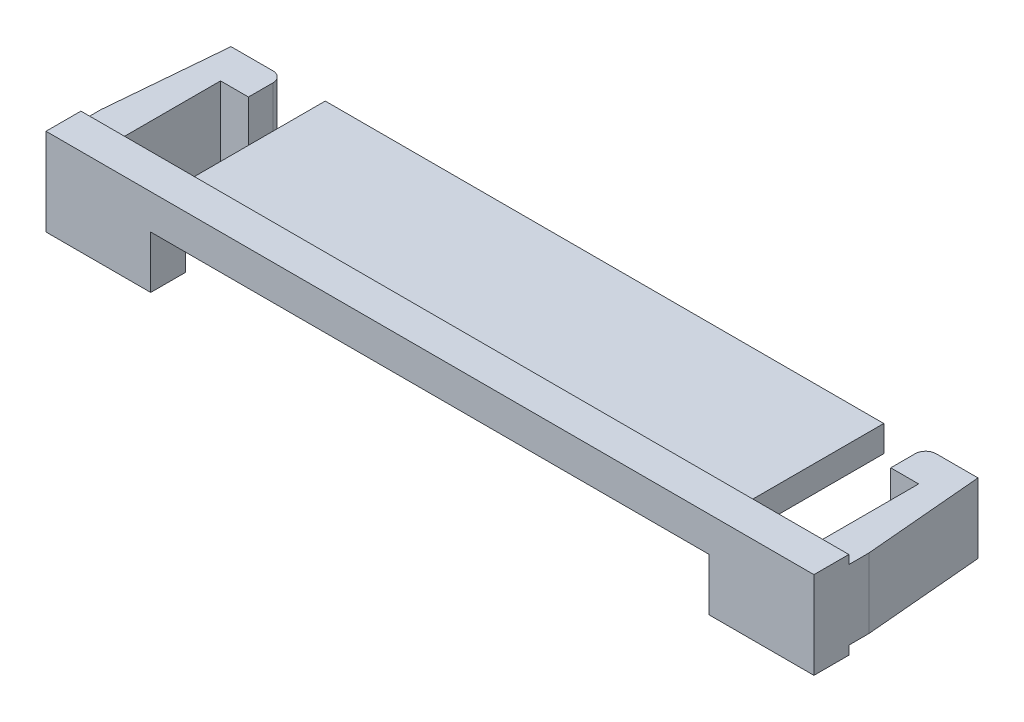
SolidWorks part; units mm, degrees
ref_plane "Front Plane" through (0, 0, 0) normal (0, 0, 1) x (1, 0, 0)
ref_plane "Top Plane" through (0, 0, 0) normal (0, 1, 0) x (1, 0, 0)
ref_plane "Right Plane" through (0, 0, 0) normal (1, 0, 0) x (0, 0, -1)
sketch "Sketch1" plane through (0, 0, 0) normal (0, 0, 1) x (1, 0, 0)
  line L1 (-11, 1.25) -> (11, 1.25)
  line L2 (-11, 1.25) -> (-11, -1.25)
  line L3 (-11, -1.25) -> (11, -1.25)
  line L4 (11, 1.25) -> (11, -1.25)
  line L5 (-11, 1.25) -> (11, -1.25) construction
  line L6 (-11, -1.25) -> (11, 1.25) construction
  point P0 (0, 0)
  dimension "D1" = 22
  dimension "D2" = 2.5
extrude "Boss-Extrude1" add sketch "Sketch1" along normal blind 5
sketch "Sketch2" plane through (0, 0, 0) normal (0, 0, -1) x (-1, 0, 0)
  line L0 (11, 1.25) -> (11, -1.25) construction
  line L1 (-11, 1.25) -> (11, 1.25)
  line L2 (-11, 1.25) -> (-11, 1)
  line L3 (-11, 1) -> (11, 1)
  line L4 (11, 1.25) -> (11, 1)
  line L5 (-11, -1.25) -> (-11, 1.25) construction
  line L6 (11, -1.25) -> (-11, -1.25)
  line L7 (11, -1.25) -> (11, -1)
  line L8 (11, -1) -> (-11, -1)
  line L9 (-11, -1.25) -> (-11, -1)
  dimension "D1" = 0.25
  dimension "D2" = 0.25
extrude "Cut-Extrude1" cut sketch "Sketch2" against normal blind 4
sketch "Sketch3" plane through (0, 0, 0) normal (0, 0, -1) x (-1, 0, 0)
  line L0 (-11, 1) -> (11, 1) construction
  line L1 (-10, 1) -> (-8, 1)
  line L2 (-10, 1) -> (-10, -1)
  line L3 (-10, -1) -> (-8, -1)
  line L4 (-8, 1) -> (-8, -1)
  line L5 (11, -1) -> (-11, -1) construction
  line L6 (-11, -1) -> (-11, 1) construction
  line L7 (10, 1) -> (8, 1)
  line L8 (10, 1) -> (10, -1)
  line L9 (10, -1) -> (8, -1)
  line L10 (8, 1) -> (8, -1)
  line L11 (11, 1) -> (11, -1) construction
  dimension "D1" = 1
  dimension "D2" = 1
  dimension "D3" = 2
  dimension "D4" = 2
extrude "Cut-Extrude2" cut sketch "Sketch3" against normal blind 4
sketch "Sketch5" plane through (0, 0, 0) normal (0, 0, -1) x (-1, 0, 0)
  line L0 (-8, -1) -> (-8, 1) construction
  line L1 (-8, 0.25) -> (8, 0.25)
  line L2 (-8, 0.25) -> (-8, -1.25)
  line L3 (-8, -1.25) -> (8, -1.25)
  line L4 (8, 0.25) -> (8, -1.25)
  line L5 (-11, -1.25) -> (11, -1.25) construction
  line L6 (8, 1) -> (8, -1) construction
  line L7 (11, 1.25) -> (-11, 1.25) construction
  dimension "D1" = 1
extrude "Cut-Extrude3" cut sketch "Sketch5" against normal blind 5
sketch "Sketch6" plane through (0, 1, 0) normal (0, 1, 0) x (1, 0, 0)
  line L1 (-11, 0) -> (-9.2, 0)
  line L2 (-11, 0) -> (-11, -1)
  line L3 (-11, -1) -> (-9.2, -1)
  line L4 (-9.2, 0) -> (-9.2, -1)
  line L5 (11, 0) -> (9.2, 0)
  line L6 (11, 0) -> (11, -1)
  line L7 (11, -1) -> (9.2, -1)
  line L8 (9.2, 0) -> (9.2, -1)
  dimension "D1" = 1.8
  dimension "D2" = 1.8
  dimension "D3" = 1
  dimension "D4" = 1
extrude "Boss-Extrude2" add sketch "Sketch6" against normal blind 2
fillet "Fillet1" radius 0.3 2 edges at (9.2, 0, 0) (-9.2, 0, 0)
chamfer "Chamfer1" distance 0.3 angle 85 2 edges at (11, 0, 0) (-11, 0, 0) first distance on face at (10.25, 0, 0) first distance on face at (-10.25, 0, 0)
